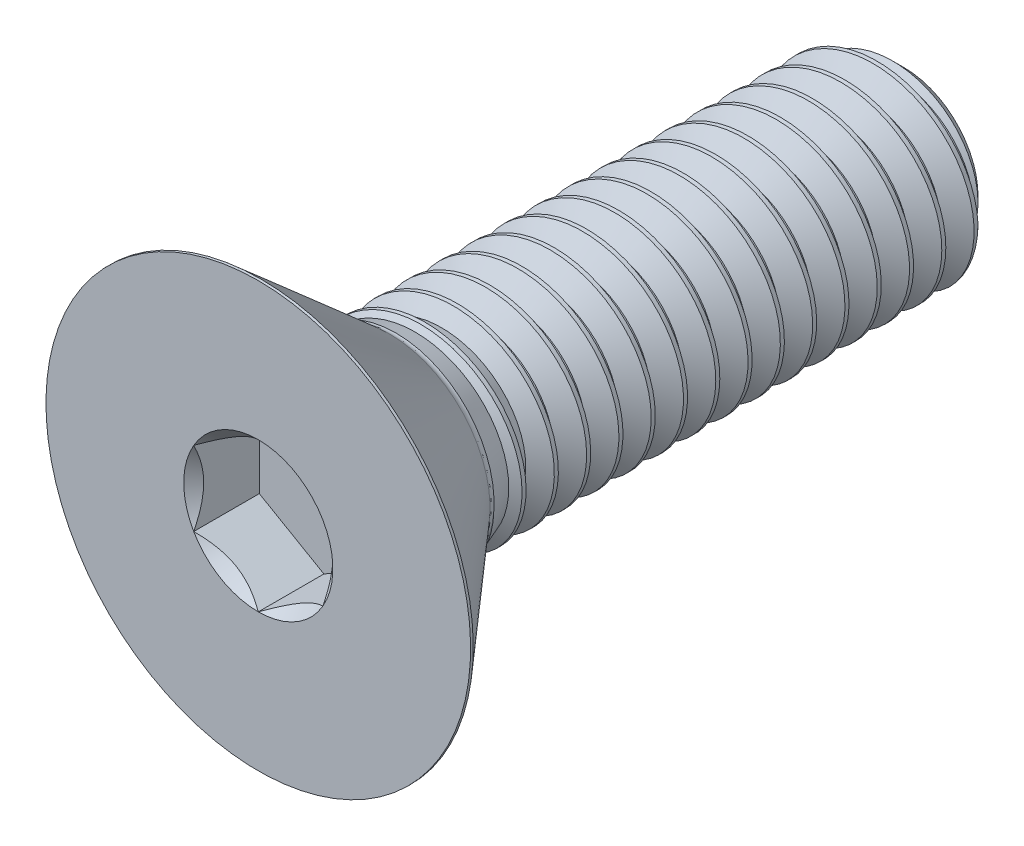
SolidWorks part; units mm, degrees
ref_plane "Front Plane" through (0, 0, 0) normal (0, 0, 1) x (1, 0, 0)
ref_plane "Top Plane" through (0, 0, 0) normal (0, 1, 0) x (1, 0, 0)
ref_plane "Right Plane" through (0, 0, 0) normal (1, 0, 0) x (0, 0, -1)
sketch "Sketch1" plane through (0, 0, 0) normal (1, 0, 0) x (0, 0, -1)
  line L0 (-7.9375, 0) -> (7.9375, 0) construction
  line L1 (-7.9375, 0) -> (-7.9375, 5.2197)
  line L2 (-7.9375, 5.2197) -> (-7.873, 5.2197)
  line L3 (-7.873, 5.2197) -> (-4.7117, 2.4716)
  line L4 (-7.873, -5.2197) -> (-4.7117, -2.4716)
  line L5 (7.9375, 0) -> (7.9375, 2.413)
  line L6 (7.9375, 2.413) -> (-4.7117, 2.413)
  line L7 (7.3422, 2.413) -> (7.9375, 1.8177)
  line L8 (7.8879, 2.4989) -> (8.2848, 1.8115) construction
  line L9 (8.2848, 1.8115) -> (8.6816, 2.4989) construction
  line L10 (8.6816, 2.4989) -> (7.8879, 2.4989) construction
  line L11 (7.9127, 2.456) -> (8.6568, 2.456)
  line L12 (8.6568, 2.456) -> (8.3344, 1.8974)
  line L13 (8.3344, 1.8974) -> (8.2352, 1.8974)
  line L14 (8.2352, 1.8974) -> (7.9127, 2.456)
  line L15 (8.2848, 1.8974) -> (8.2848, 1.8115) construction
  line L16 (7.9375, 2.413) -> (8.632, 2.413) construction
  line L17 (8.2848, 2.4989) -> (8.2848, 2.413) construction
  line L18 (7.9375, -2.413) -> (-4.7117, -2.413)
  arc A0 (-4.7117, 2.4716) -> (-4.5549, 2.413) centre (-4.5549, 2.6521) ccw
  point P2 (0, 0)
  point P23 (-6.3246, 0)
  point P27 (8.2848, 2.456)
  point P30 (6.7469, -2.413)
  point P34 (-7.873, -5.2197)
  dimension "Length" = 15.875
  dimension "Head Height" = 3.2258
  dimension "Head Diameter" = 10.4394
  dimension "Countersink Angle" = 82
  dimension "Thread Diameter" = 4.826
  dimension "D2" = 0.0645
  dimension "Pitch" = 0.7937
  dimension "D4" = 0.0992
  dimension "D3" = 45
  dimension "D5" = 0.5953
  dimension "D6" = 1.6129
  dimension "D1" = 1.1906
sketch "Sketch2" plane through (0, 0, 0) normal (0, 0, 1) x (1, 0, 0)
  line L1 (0, 1.8331) -> (-1.5875, 0.9165)
  line L2 (-1.5875, 0.9165) -> (-1.5875, -0.9165)
  line L3 (-1.5875, -0.9165) -> (0, -1.8331)
  line L4 (0, -1.8331) -> (1.5875, -0.9165)
  line L5 (1.5875, -0.9165) -> (1.5875, 0.9165)
  line L6 (1.5875, 0.9165) -> (0, 1.8331)
  circle A0 centre (0, 0) radius 1.5875 construction
  dimension "Drive Size" = 3.175
sketch "Sketch11" plane through (0, 0, 0) normal (1, 0, 0) x (0, 0, -1)
  line L0 (-7.873, 5.2197) -> (-4.7117, 2.4716) construction
  line L1 (-7.9375, 0) -> (-7.9375, 5.2197) construction
  line L2 (-7.873, 5.2197) -> (-4.7117, 2.4716)
  line L3 (-7.9375, 0) -> (-7.9375, 5.2197)
  line L4 (-7.9375, 5.2197) -> (-7.873, 5.2197) construction
  line L5 (-7.9375, 5.2197) -> (-7.873, 5.2197)
  line L6 (-4.5549, 2.413) -> (7.3422, 2.413)
  line L7 (7.3422, 2.413) -> (7.9375, 1.8177)
  line L8 (7.9375, 1.8177) -> (7.9375, 0)
  line L9 (7.9375, 0) -> (-7.9375, 0)
  arc A0 (-4.7117, 2.4716) -> (-4.5549, 2.413) centre (-4.5549, 2.6521) ccw construction
  arc A1 (-4.7117, 2.4716) -> (-4.5549, 2.413) centre (-4.5549, 2.6521) ccw
revolve "Revolve1" add sketch "Sketch11" angle 360 about L9
sketch "Sketch9" plane through (0, 0, 7.9375) normal (0, 0, 1) x (1, 0, 0)
  line L0 (1.5875, -0.9165) -> (1.5875, 0.9165) construction
  line L1 (0, -1.8331) -> (1.5875, -0.9165) construction
  line L2 (-1.5875, -0.9165) -> (0, -1.8331) construction
  line L3 (-1.5875, 0.9165) -> (-1.5875, -0.9165) construction
  line L4 (0, 1.8331) -> (-1.5875, 0.9165) construction
  line L5 (1.5875, 0.9165) -> (0, 1.8331) construction
  line L6 (1.5875, -0.9165) -> (1.5875, 0.9165)
  line L7 (0, -1.8331) -> (1.5875, -0.9165)
  line L8 (-1.5875, -0.9165) -> (0, -1.8331)
  line L9 (-1.5875, 0.9165) -> (-1.5875, -0.9165)
  line L10 (0, 1.8331) -> (-1.5875, 0.9165)
  line L11 (1.5875, 0.9165) -> (0, 1.8331)
sketch "Sketch10" plane through (0, 0, 7.9375) normal (0, 0, 1) x (1, 0, 0)
  circle A0 centre (0, 0) radius 1.8331
extrude "Cut-Extrude2" cut sketch "Sketch10" against normal up to vertex (1.6129 mm away) draft 45 up to point (0, 0, 6.3246)
extrude "Cut-Extrude1" cut sketch "Sketch9" against normal up to vertex (1.6129 mm away) up to point (0, 0, 6.3246)
ref_plane "Plane1" through (0, 0, 4.5549) normal (0, 0, 1) x (1, 0, 0)
split "Split1" trim tools "Plane1" bodies to split 111 resulting bodies 105 106
sketch "Sketch3" plane through (0, 0, -7.9375) normal (0, 0, -1) x (-1, 0, 0)
  circle A0 centre (0, 0) radius 2.413 construction
  circle A1 centre (0, 0) radius 2.413
curve "Helix/Spiral1" pitch 0.7937 height 15.875 turns 20
sketch "Sketch4" plane through (0, 0, 0) normal (1, 0, 0) x (0, 0, -1)
  line L0 (7.9127, 2.456) -> (8.6568, 2.456) construction
  line L1 (8.2352, 1.8974) -> (7.9127, 2.456) construction
  line L2 (8.3344, 1.8974) -> (8.2352, 1.8974) construction
  line L3 (8.6568, 2.456) -> (8.3344, 1.8974) construction
  line L4 (7.9127, 2.456) -> (8.6568, 2.456)
  line L5 (8.2352, 1.8974) -> (7.9127, 2.456)
  line L6 (8.3344, 1.8974) -> (8.2352, 1.8974)
  line L7 (8.6568, 2.456) -> (8.3344, 1.8974)
sweep "Cut-Sweep1" cut profiles "Sketch4" path "Helix/Spiral1"
sketch "Sketch7" plane through (0, 0, 4.5549) normal (0, 0, 1) x (1, 0, 0)
  circle A0 centre (0, 0) radius 2.413
extrude "Boss-Extrude2" add sketch "Sketch7" against normal up to next (12.4924 mm away) draft 20
equation "\"D2@Sketch1\"=\"Head Height@Sketch1\"/50"
equation "\"D4@Sketch1\" = \"Pitch@Sketch1\" / 8"
equation "\"D5@Sketch1\"=\"Pitch@Sketch1\"*0.75"
equation "\"D4@Helix/Spiral1\"=\"Pitch@Sketch1\""
equation "\"D3@Helix/Spiral1\"=\"Length@Sketch1\""
equation "\"D6@Sketch1\"=\"Head Height@Sketch1\"/2"
equation "\"D1@Sketch1\"=\"Pitch@Sketch1\"*1.5"
